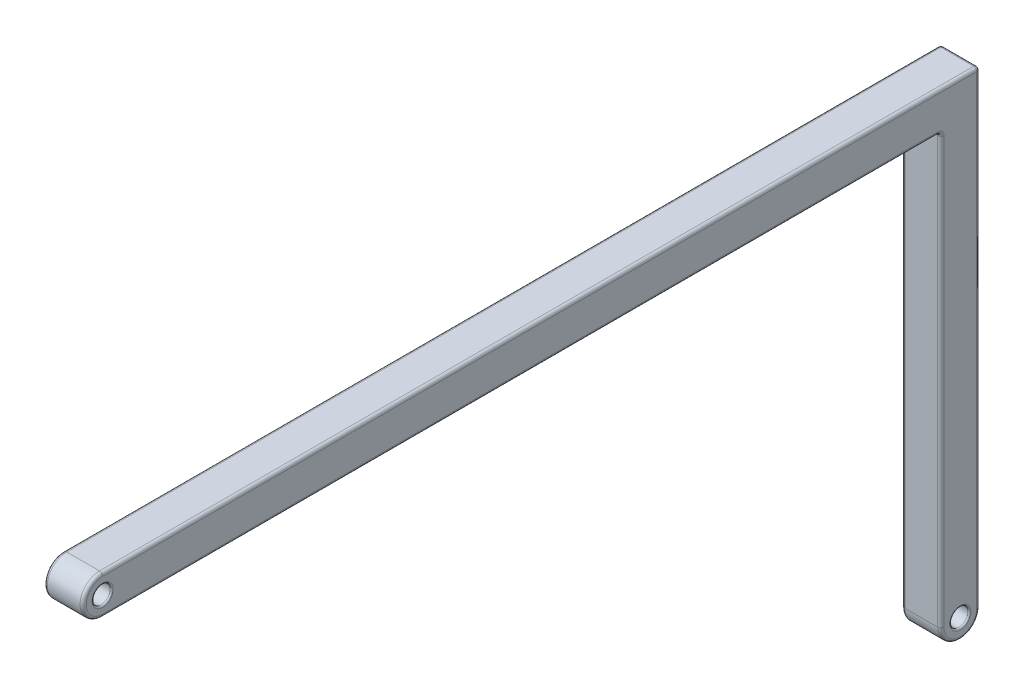
SolidWorks part; units mm, degrees
ref_plane "Front Plane" through (0, 0, 0) normal (0, 0, 1) x (1, 0, 0)
ref_plane "Top Plane" through (0, 0, 0) normal (0, 1, 0) x (1, 0, 0)
ref_plane "Right Plane" through (0, 0, 0) normal (1, 0, 0) x (0, 0, -1)
sketch "Sketch1" plane through (0, 0, 0) normal (1, 0, 0) x (0, 0, -1)
  line L1 (0, 0) -> (55, 0)
  line L8 (0, 0) -> (0, -2.5) construction
  line L12 (55, 0) -> (55, -2.5) construction
  line L13 (0, -2.5) -> (53.75, -2.5)
  line L16 (55, -1.25) -> (56.25, -1.25) construction
  line L17 (55, 0) -> (56.25, 0)
  line L18 (56.25, 0) -> (56.25, -30)
  line L19 (56.25, -30) -> (53.75, -30) construction
  line L20 (53.75, -30) -> (53.75, -2.5)
  circle A0 centre (0, -1.25) radius 0.575
  arc A1 (0, -2.5) -> (0, 0) centre (0, -1.25) cw
  arc A4 (53.75, -30) -> (56.25, -30) centre (55, -30) ccw
  circle A5 centre (55, -30) radius 0.575
  dimension "D1" = 1.15
  dimension "D4" = 1.25
  dimension "D3" = 55
  dimension "D7" = 1.15
  dimension "D2" = 2.5
  dimension "D5" = 30
  dimension "D6" = 2.5
extrude "Boss-Extrude1" add sketch "Sketch1" along normal blind 2.5
fillet "Fillet2" radius 0.1 4 edges at (0, -1.25, -0.575) (2.5, -1.25, -0.575) (0, -30, -55.575) (2.5, -30, -55.575)
fillet "Fillet3" radius 0.2 14 edges at (2.5, -2.5, -26.875) (2.5, -1.25, 1.25) (0, -2.5, -26.875) (0, -1.25, 1.25) (2.5, -15, -56.25) (2.5, -31.25, -55) (0, -15, -56.25) (0, -31.25, -55) (1.25, 0, -56.25) (2.5, 0, -28.125) (0, 0, -28.125) (1.25, -2.5, -53.75) (2.5, -16.25, -53.75) (0, -16.25, -53.75)
